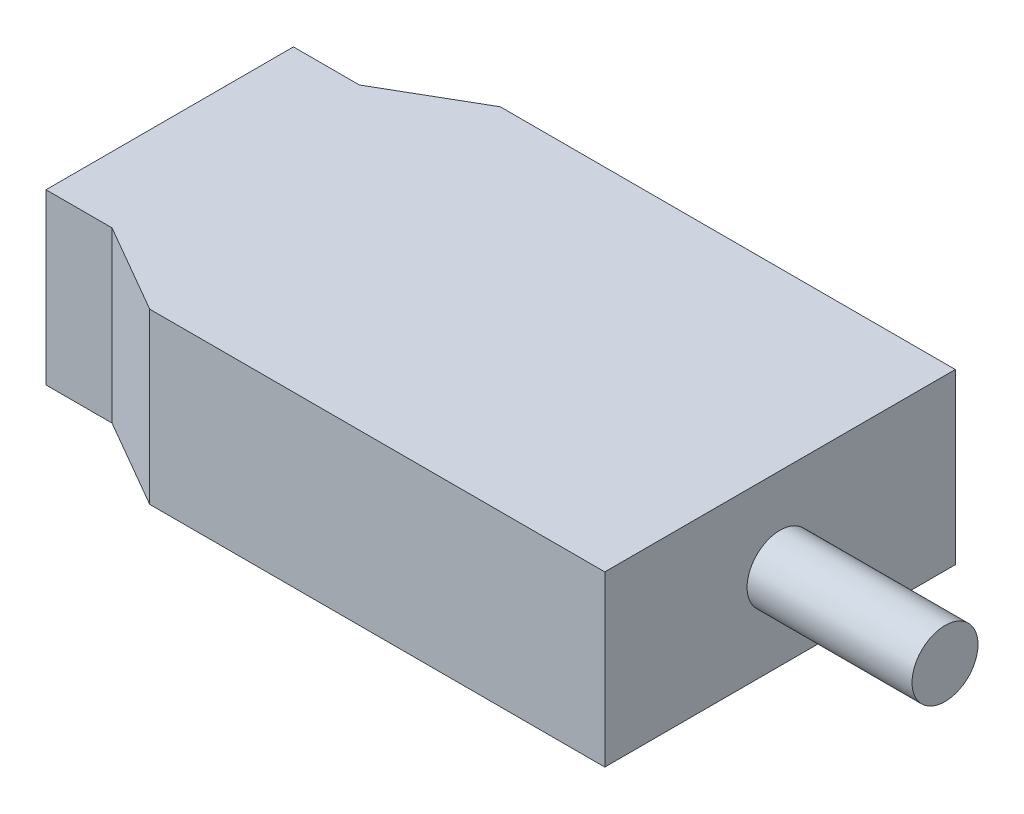
SolidWorks part; units mm, degrees
ref_plane "Vorne" through (0, 0, 0) normal (0, 0, 1) x (1, 0, 0)
ref_plane "Oben" through (0, 0, 0) normal (0, 1, 0) x (1, 0, 0)
ref_plane "Rechts" through (0, 0, 0) normal (1, 0, 0) x (0, 0, -1)
sketch "Skizze1" plane through (0, 0, 0) normal (0, 1, 0) x (1, 0, 0)
  line L0 (0, 21.25) -> (0, -21.25)
  line L1 (0, -21.25) -> (-55.1747, -21.25)
  line L2 (-74, 15) -> (-66, 15)
  line L3 (-74, -15) -> (-74, 15)
  line L4 (-66, 15) -> (-55.1747, 21.25)
  line L5 (-55.1747, 21.25) -> (0, 21.25)
  line L6 (-74, -15) -> (-66, -15)
  line L7 (-66, -15) -> (-55.1747, -21.25)
  dimension "D1" = 42.5
  dimension "D2" = 74
  dimension "D3" = 8
  dimension "D4" = 30
  dimension "D5" = 30
extrude "Aufsatz-Linear austragen1" add sketch "Skizze1" along normal blind 10.25 and the other way blind 10.25
sketch "Skizze2" plane through (0, 0, 0) normal (1, 0, 0) x (0, 0, -1)
  circle A0 centre (0, 0) radius 4
  dimension "D1" = 8
extrude "Aufsatz-Linear austragen2" add sketch "Skizze2" along normal blind 20
